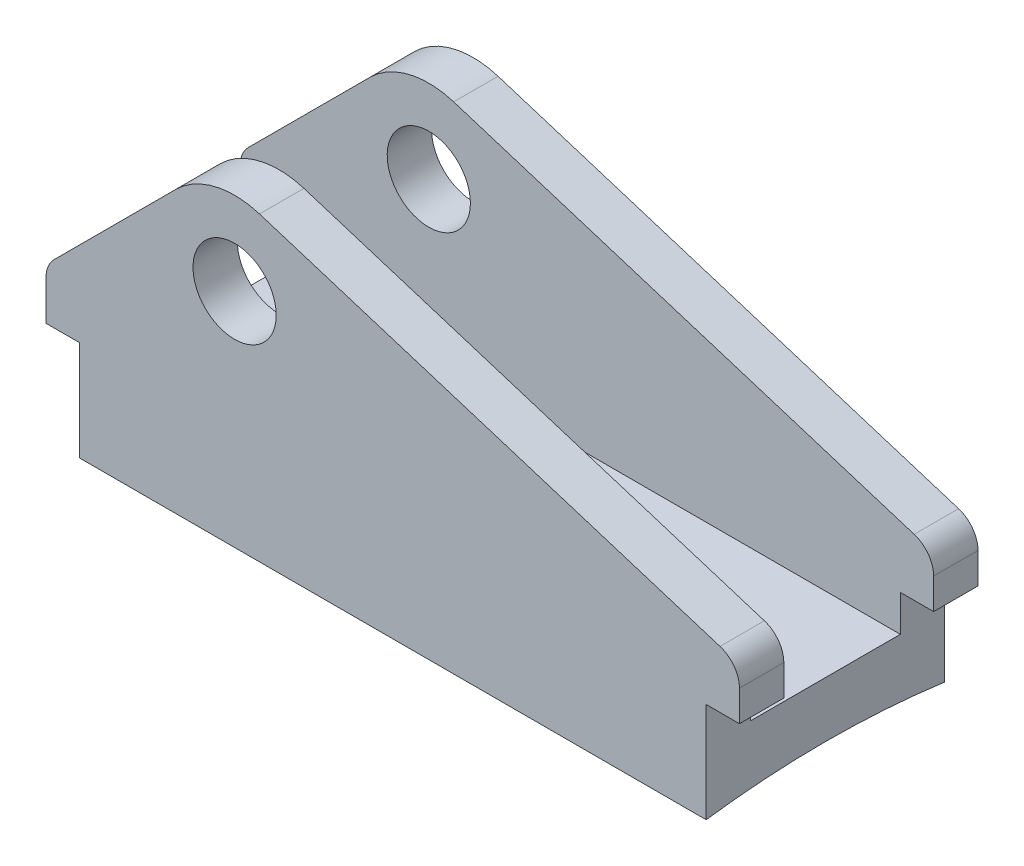
SolidWorks part; units mm, degrees
ref_plane "Front Plane" through (0, 0, 0) normal (0, 0, 1) x (1, 0, 0)
ref_plane "Top Plane" through (0, 0, 0) normal (0, 1, 0) x (1, 0, 0)
ref_plane "Right Plane" through (0, 0, 0) normal (1, 0, 0) x (0, 0, -1)
sketch "Sketch1" plane through (0, 0, 0) normal (0, 1, 0) x (1, 0, 0)
  line L1 (-62.5, -21.5) -> (62.5, -21.5)
  line L2 (-62.5, -21.5) -> (-62.5, 21.5)
  line L3 (-62.5, 21.5) -> (62.5, 21.5)
  line L4 (62.5, -21.5) -> (62.5, 21.5)
  line L5 (-62.5, -21.5) -> (62.5, 21.5) construction
  line L6 (-62.5, 21.5) -> (62.5, -21.5) construction
  point P0 (0, 0)
  dimension "D1" = 125
  dimension "D2" = 43
extrude "Boss-Extrude1" add sketch "Sketch1" along normal blind 55
sketch "Sketch2" plane through (0, 0, 21.5) normal (0, 0, 1) x (1, 0, 0)
  line L0 (-56.5, 0) -> (-56.5, 18)
  line L1 (-62.5, 0) -> (62.5, 0) construction
  line L2 (-56.5, 18) -> (-62.5, 18)
  line L3 (-62.5, 55) -> (-62.5, 0) construction
  line L4 (-62.5, 18) -> (-62.5, 25.1421)
  line L5 (-61.0355, 28.6777) -> (-39.1066, 50.6066)
  line L6 (-62.5, 55) -> (62.5, 55) construction
  line L7 (-24.0161, 54.3142) -> (58.9946, 28.3113)
  line L8 (62.5, 55) -> (62.5, 0) construction
  line L9 (0, 0) -> (0, 19.0979) construction
  line L10 (56.5, 18) -> (62.5, 18)
  line L11 (56.5, 0) -> (56.5, 18)
  line L12 (62.5, 23.5399) -> (62.5, 18)
  line L13 (56.5, 0) -> (-56.5, 0)
  circle A0 centre (-28.5, 40) radius 15
  circle A1 centre (-28.5, 40) radius 7.5
  arc A2 (58.9946, 28.3113) -> (62.5, 23.5399) centre (57.5, 23.5399) cw
  arc A3 (-62.5, 25.1421) -> (-61.0355, 28.6777) centre (-57.5, 25.1421) cw
  point P23 (0, 0)
  point P24 (0, 0)
  point P28 (62.5, 27.2132)
  point P31 (-62.5, 27.2132)
  line M1 (-62.5, 0) -> (62.5, 0)
  line M2 (62.5, 0) -> (62.5, 55)
  line M4 (-62.5, 55) -> (-62.5, 0)
  dimension "D1" = 30
  dimension "D2" = 15
  dimension "D7" = 5
  dimension "D3" = 45
  dimension "D4" = 34
  dimension "D5" = 6
  dimension "D6" = 18
extrude "Cut-Extrude1" cut sketch "Sketch2" against normal through all flip side to cut contours A0 A1 | A3 L2 L0 L13 L11 L10 A2 L7 A0 L5 M4 M1 M2 region at (0.0377, 19.5262, 21.5) region at (-31.9777, 54.1548, 21.5)
sketch "Sketch8" plane through (56.5, 0, 0) normal (1, 0, 0) x (0, 0, -1)
  line L0 (0, 0) -> (0, -78.6168) construction
  circle A0 centre (0, -158.5489) radius 160
  point P5 (0, -118.6557)
  point P6 (0, -162.3176)
  dimension "D1" = 320
extrude "Cut-Extrude3" cut sketch "Sketch8" against normal through all
sketch "Sketch3" plane through (62.5, 0, 0) normal (1, 0, 0) x (0, 0, -1)
  line L0 (21.5, 55) -> (-21.5, 55) construction
  line L1 (-13.5, 55) -> (13.5, 55)
  line L2 (-13.5, 55) -> (-13.5, 11.4511)
  line L3 (-13.5, 11.4511) -> (13.5, 11.4511)
  line L4 (13.5, 55) -> (13.5, 11.4511)
  line L5 (0, 55) -> (0, 11.4511) construction
  arc A0 (21.5, 0) -> (-21.5, 0) centre (0, -158.5489) ccw construction
  line M1 (21.5, 23.5399) -> (-21.5, 23.5399)
  line M3 (-21.5, 18) -> (21.5, 18)
  dimension "D1" = 27
  dimension "D2" = 170
extrude "Cut-Extrude2" cut sketch "Sketch3" against normal through all contours L5 L1 L2 M1 | L1 L5 L4 M1 | L5 L4 M1 M3 | L5 L2 M1 M3 | L5 L2 L3 M3 | L5 L3 L4 M3 region at (62.5, 39.2699, 6.75) region at (62.5, 39.2699, -6.75) region at (62.5, 20.7699, 6.75) region at (62.5, 20.7699, -6.75) region at (62.5, 14.7256, 6.75) region at (62.5, 14.7256, -6.75)
